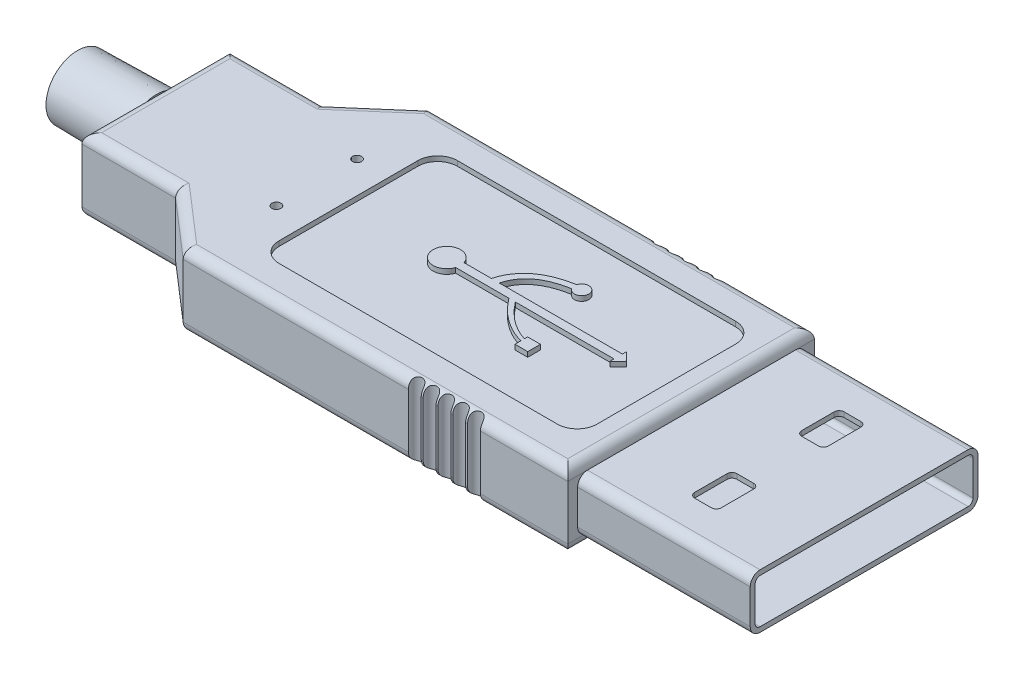
SolidWorks part; units mm, degrees
ref_plane "Alzado" through (0, 0, 0) normal (0, 0, 1) x (1, 0, 0)
ref_plane "Planta" through (0, 0, 0) normal (0, 1, 0) x (1, 0, 0)
ref_plane "Vista lateral" through (0, 0, 0) normal (1, 0, 0) x (0, 0, -1)
sketch "Croquis1" plane through (0, 0, 0) normal (0, 1, 0) x (1, 0, 0)
  line L0 (41.1135, -0.0966) -> (-102.5418, -0.0966) construction
  line L1 (38.9948, 24.9034) -> (38.9948, -25.0966)
  line L2 (-38.9948, 24.9034) -> (-50.5365, 14.9034)
  line L3 (38.9948, 24.9034) -> (-38.9948, 24.9034)
  line L4 (38.9948, -25.0966) -> (-38.9948, -25.0966)
  line L5 (0, 0) -> (-38.9948, 24.9034) construction
  line L6 (38.9948, 24.9034) -> (0, 0) construction
  line L7 (-50.5365, 14.9034) -> (-69.5303, 14.9034)
  line L8 (-38.9948, -25.0966) -> (-50.5365, -15.0966)
  line L9 (-50.5365, -15.0966) -> (-69.5303, -15.0966)
  line L10 (-69.5303, 14.9034) -> (-69.5303, -15.0966)
  point P0 (0, 0)
  point P12 (38.9948, -0.0966)
  point P15 (-69.5303, -0.0966)
  dimension "D1" = 15
  dimension "D2" = 25
extrude "Saliente-Extruir1" add sketch "Croquis1" along normal mid plane 15
fillet "Redondeo1" radius 2 16 edges at (-44.7656, -7.5, -19.9034) (-60.0334, -7.5, -14.9034) (-69.5303, -7.5, 0.0966) (-60.0334, -7.5, 15.0966) (-44.7656, -7.5, 20.0966) (0, -7.5, 25.0966) (38.9948, -7.5, 0.0966) (0, -7.5, -24.9034) (38.9948, 7.5, 0.0966) (0, 7.5, 25.0966) (-44.7656, 7.5, 20.0966) (-60.0334, 7.5, 15.0966) (-69.5303, 7.5, 0.0966) (-60.0334, 7.5, -14.9034) (-44.7656, 7.5, -19.9034) (0, 7.5, -24.9034)
sketch "Croquis2" plane through (38.9948, 0, 0) normal (1, 0, 0) x (0, 0, -1)
  line L0 (24.9034, 5.5) -> (-25.0966, 5.5) construction
  line L1 (-21.0966, -5.5) -> (21.0966, -5.5)
  line L2 (-23.0966, -3.5) -> (-23.0966, 3.5)
  line L3 (-21.0966, 5.5) -> (21.0966, 5.5)
  line L4 (23.0966, -3.5) -> (23.0966, 3.5)
  line L5 (-23.0966, -5.5) -> (23.0966, 5.5) construction
  line L6 (-23.0966, 5.5) -> (23.0966, -5.5) construction
  line L8 (-25.0966, 5.5) -> (-25.0966, -5.5) construction
  arc A0 (21.0966, 5.5) -> (23.0966, 3.5) centre (21.0966, 3.5) cw
  arc A1 (21.0966, -5.5) -> (23.0966, -3.5) centre (21.0966, -3.5) ccw
  arc A2 (-21.0966, -5.5) -> (-23.0966, -3.5) centre (-21.0966, -3.5) cw
  arc A3 (-23.0966, 3.5) -> (-21.0966, 5.5) centre (-21.0966, 3.5) cw
  point P0 (0, 0)
  dimension "D2" = 2
  dimension "D1" = 2
extrude "Extruir-Lámina1" add sketch "Croquis2" along normal blind 35 thin thin type one direction reverse wall 1
sketch "Croquis3" plane through (0, 7.5, 0) normal (0, 1, 0) x (1, 0, 0)
  line L0 (-38.9948, 24.9034) -> (38.9948, 24.9034) construction
  line L1 (0, 0) -> (44.7527, 0) construction
  line L3 (-26.5656, -18.074) -> (29.8829, -18.074)
  line L4 (-30.5656, -14.074) -> (-30.5656, 14.074)
  line L5 (-26.5656, 18.074) -> (29.8829, 18.074)
  line L6 (33.8829, -14.074) -> (33.8829, 14.074)
  line L7 (-30.5656, -18.074) -> (33.8829, 18.074) construction
  line L8 (-30.5656, 18.074) -> (33.8829, -18.074) construction
  circle A0 centre (19.9736, 24.9034) radius 1.3143
  circle A1 centre (16.9736, 24.9034) radius 1.3143
  circle A2 centre (13.9736, 24.9034) radius 1.3143
  circle A3 centre (10.9736, 24.9034) radius 1.3143
  circle A4 centre (7.9736, 24.9034) radius 1.3143
  circle A5 centre (7.9736, -24.9034) radius 1.3143
  circle A6 centre (10.9736, -24.9034) radius 1.3143
  circle A7 centre (13.9736, -24.9034) radius 1.3143
  circle A8 centre (16.9736, -24.9034) radius 1.3143
  circle A9 centre (19.9736, -24.9034) radius 1.3143
  arc A10 (29.8829, 18.074) -> (33.8829, 14.074) centre (29.8829, 14.074) cw
  arc A11 (29.8829, -18.074) -> (33.8829, -14.074) centre (29.8829, -14.074) ccw
  arc A12 (-26.5656, -18.074) -> (-30.5656, -14.074) centre (-26.5656, -14.074) cw
  arc A13 (-30.5656, 14.074) -> (-26.5656, 18.074) centre (-26.5656, 14.074) cw
  point P25 (1.6587, 0)
  dimension "D2" = 4
  dimension "D1" = 5
extrude "Cortar-Extruir1" cut sketch "Croquis3" against normal through all contours A5 | A6 | A7 | A8 | A9 | A4 | A3 | A2 | A0 | A2 | A1 region at (19.9736, 7.5, -24.9034) region at (13.9736, 7.5, -24.9034) region at (10.9736, 7.5, -24.9034) region at (7.9736, 7.5, -24.9034) region at (7.9736, 7.5, 24.9034) region at (10.9736, 7.5, 24.9034) region at (13.9736, 7.5, 24.9034) region at (16.9736, 7.5, 24.9034) region at (19.9736, 7.5, 24.9034)
extrude "Cortar-Extruir2" cut sketch "Croquis3<3>" against normal blind 1 contours A13 L4 A12 L3 A11 L6 A10 L5 region at (1.6587, 7.5, 0)
sketch "Croquis3<3>" plane through (0, 7.5, 0) normal (0, 1, 0) x (1, 0, 0) same geometry as "Croquis3"
mirror "Simetría3" about plane through (0, 0, 0) normal (0, 1, 0) of "Cortar-Extruir2"
sketch "Croquis4" plane through (0, 6.5, 0) normal (0, 1, 0) x (1, 0, 0)
  line L0 (25.8518, 0) -> (24.1589, 1.665)
  line L1 (24.1589, 1.665) -> (24.1589, -1.7214)
  line L2 (24.1589, -1.7214) -> (25.8518, 0)
  line L3 (24.1589, 0.8229) -> (-7.9588, 0.8229)
  line L4 (-10.6038, -0.0282) -> (24.1589, -0.0282) construction
  line L5 (24.1589, -0.8792) -> (-7.9588, -0.8792)
  line L6 (11.5293, -6.4051) -> (11.5293, -5.7707)
  line L7 (11.5293, -8.3455) -> (14.121, -8.3455)
  line L8 (11.5293, -8.3455) -> (11.5293, -7.1221)
  line L9 (11.5293, -5.7707) -> (14.121, -5.7707)
  line L10 (14.121, -8.3455) -> (14.121, -5.7707)
  circle A0 centre (-10.6038, -0.0282) radius 2.7785
  arc A1 (7.5291, 7.1708) -> (7.3466, 8.3914) centre (8.7448, 7.9765) ccw
  spline S3 degree 3 poles (7.3466, 8.3914) (7.0564, 8.3404) (6.0814, 8.1495) (4.5235, 7.7272) (2.7963, 7.0282) (0.7763, 5.858) (-0.8012, 4.3125) (-1.8828, 2.4291) (-2.2615, 1.3616) (-2.4044, 0.8229) knots 0.074013 0.074013 0.074013 0.074013 0.125 0.25 0.375 0.5 0.75 0.875 1 1 1 1
  spline S5 degree 3 poles (7.5291, 7.1708) (7.2956, 7.1286) (6.4299, 6.9567) (5.0419, 6.5795) (3.5149, 5.9598) (2.2188, 5.2061) (1.1472, 4.3242) (0.286, 3.3089) (-0.3731, 2.1654) (-0.6907, 1.2708) (-0.8095, 0.8229) knots 0.080522 0.080522 0.080522 0.080522 0.125 0.25 0.375 0.5 0.625 0.75 0.875 1 1 1 1
  spline S7 degree 3 poles (2.8267, -0.8792) (3.1632, -1.323) (3.8785, -2.2001) (5.349, -3.7394) (7.3255, -5.3369) (9.5392, -6.5033) (10.9858, -6.9795) (11.5293, -7.1221) knots 0 0 0 0 0.125 0.25 0.5 0.75 0.896841 0.896841 0.896841 0.896841
  spline S9 degree 3 poles (4.1414, -0.8792) (4.4534, -1.2906) (5.1192, -2.1069) (6.466, -3.5158) (8.2472, -4.9525) (10.0691, -5.9109) (11.1952, -6.3044) (11.5293, -6.4051) knots 0 0 0 0 0.125 0.25 0.5 0.75 0.853658 0.853658 0.853658 0.853658
  point P10 (12.8252, -7.0581)
extrude "Saliente-Extruir2" add sketch "Croquis4" along normal blind 1 contours A0 | S5 A1 S3 L3 | S9 L5 S7 L8 L7 L10 L9 L6 | L4 A0 L5 L1 | A0 L4 L1 L3 | L1 L2 L0 region at (24.7232, 6.5, 0.0188) region at (8.1447, 6.5, -0.3977) region at (8.1447, 6.5, 0.454) region at (-1.6069, 6.5, -0.9756) region at (7.3152, 6.5, 4.3449) region at (-7.9365, 6.5, 0.4467)
sketch "Croquis5" plane through (-69.5303, 0, 0) normal (-1, 0, 0) x (0, 0, 1)
  circle A0 centre (0, 0) radius 6.6649
extrude "Saliente-Extruir3" add sketch "Croquis5" along normal blind 16 draft 1
sketch "Croquis6" plane through (0, 5.5, 0) normal (0, 1, 0) x (1, 0, 0)
  line L0 (38.9948, 0) -> (73.9948, 0) construction
  line L1 (38.9948, 21.0966) -> (38.9948, -21.0966) construction
  line L2 (73.9948, 21.0966) -> (73.9948, -21.0966) construction
  line L3 (53.7721, -6.5648) -> (59.1731, -15.1573) construction
  line L4 (54.7721, 15.1573) -> (58.1731, 15.1573)
  line L5 (53.7721, 14.1573) -> (53.7721, 7.5648)
  line L6 (54.7721, 6.5648) -> (58.1731, 6.5648)
  line L7 (59.1731, 14.1573) -> (59.1731, 7.5648)
  line L8 (53.7721, 15.1573) -> (59.1731, 6.5648) construction
  line L9 (53.7721, 6.5648) -> (59.1731, 15.1573) construction
  line L10 (53.7721, -15.1573) -> (59.1731, -6.5648) construction
  line L11 (59.1731, -14.1573) -> (59.1731, -7.5648)
  line L12 (54.7721, -6.5648) -> (58.1731, -6.5648)
  line L13 (53.7721, -14.1573) -> (53.7721, -7.5648)
  line L14 (54.7721, -15.1573) -> (58.1731, -15.1573)
  arc A0 (53.7721, -14.1573) -> (54.7721, -15.1573) centre (54.7721, -14.1573) ccw
  arc A1 (59.1731, -14.1573) -> (58.1731, -15.1573) centre (58.1731, -14.1573) cw
  arc A2 (59.1731, -7.5648) -> (58.1731, -6.5648) centre (58.1731, -7.5648) ccw
  arc A3 (54.7721, -6.5648) -> (53.7721, -7.5648) centre (54.7721, -7.5648) ccw
  arc A4 (58.1731, 6.5648) -> (59.1731, 7.5648) centre (58.1731, 7.5648) ccw
  arc A5 (53.7721, 7.5648) -> (54.7721, 6.5648) centre (54.7721, 7.5648) ccw
  arc A6 (58.1731, 15.1573) -> (59.1731, 14.1573) centre (58.1731, 14.1573) cw
  arc A7 (54.7721, 15.1573) -> (53.7721, 14.1573) centre (54.7721, 14.1573) ccw
  point P6 (56.4726, 10.861)
  point P15 (56.4726, -10.861)
  dimension "D1" = 1
extrude "Cortar-Extruir3" cut sketch "Croquis6" against normal through all
sketch "Croquis7" plane through (0, 7.5, 0) normal (0, 1, 0) x (1, 0, 0)
  line L0 (-30.5656, 0) -> (-67.5303, -0.0966) construction
  line L1 (-30.5656, -14.074) -> (-30.5656, 14.074) construction
  line L2 (-67.5303, 12.9034) -> (-67.5303, -13.0966) construction
  circle A0 centre (-37.0151, 8.1834) radius 0.919
  circle A1 centre (-36.9723, -8.217) radius 0.919
extrude "Cortar-Extruir4" cut sketch "Croquis7" against normal through all
